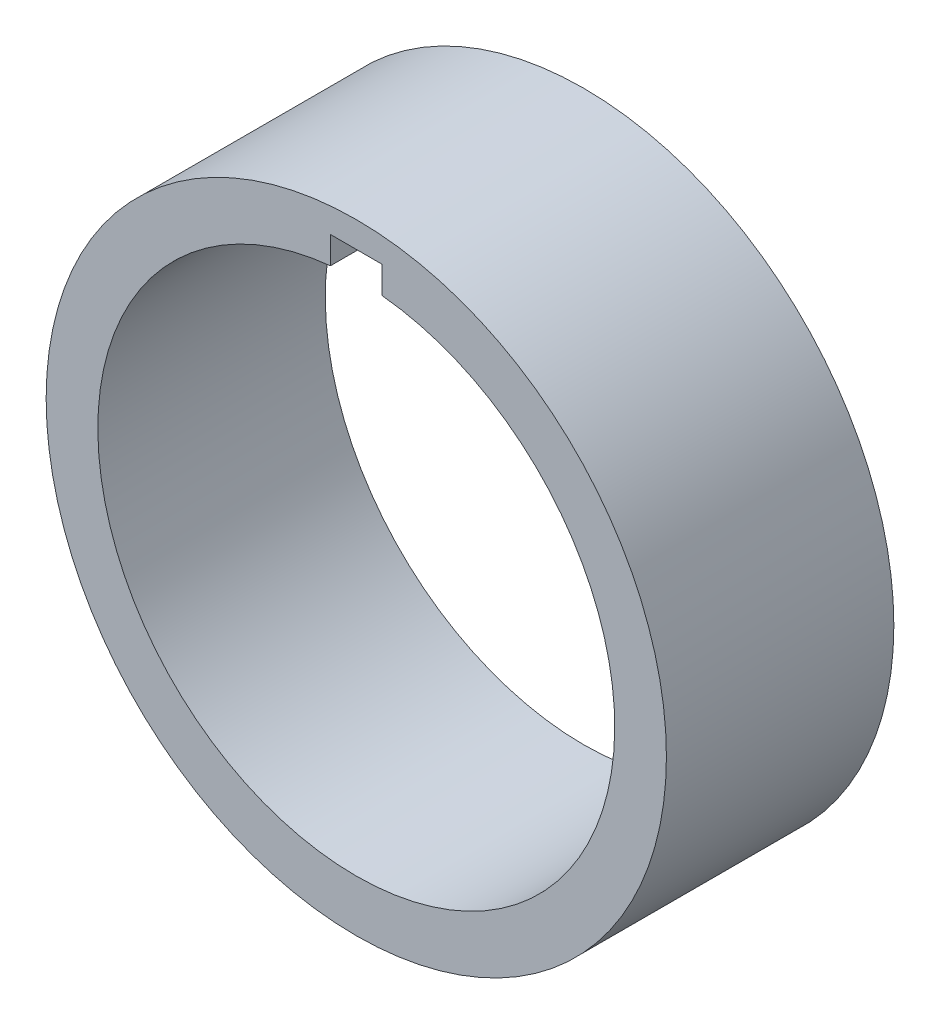
SolidWorks part; units mm, degrees
ref_plane "Front Plane" through (0, 0, 0) normal (0, 0, 1) x (1, 0, 0)
ref_plane "Top Plane" through (0, 0, 0) normal (0, 1, 0) x (1, 0, 0)
ref_plane "Right Plane" through (0, 0, 0) normal (1, 0, 0) x (0, 0, -1)
sketch "Sketch1" plane through (0, 0, 0) normal (0, 0, 1) x (1, 0, 0)
  line L3 (-2.5, 24.8747) -> (-2.5, 27.5)
  line L4 (-2.5, 27.5) -> (2.5, 27.5)
  line L5 (2.5, 27.5) -> (2.5, 24.8747)
  arc A0 (-2.5, 24.8747) -> (2.5, 24.8747) centre (0, 0) ccw
  circle A2 centre (0, 0) radius 30
  point P3 (0, 0)
  point P4 (0, 0)
  point P5 (0, 27.5)
  dimension "D1" = 5
  dimension "D2" = 50
  dimension "D3" = 5
  dimension "D5" = 27.5
extrude "Boss-Extrude1" add sketch "Sketch1" along normal blind 22 contours A2 | A0 L5 L4 L3
